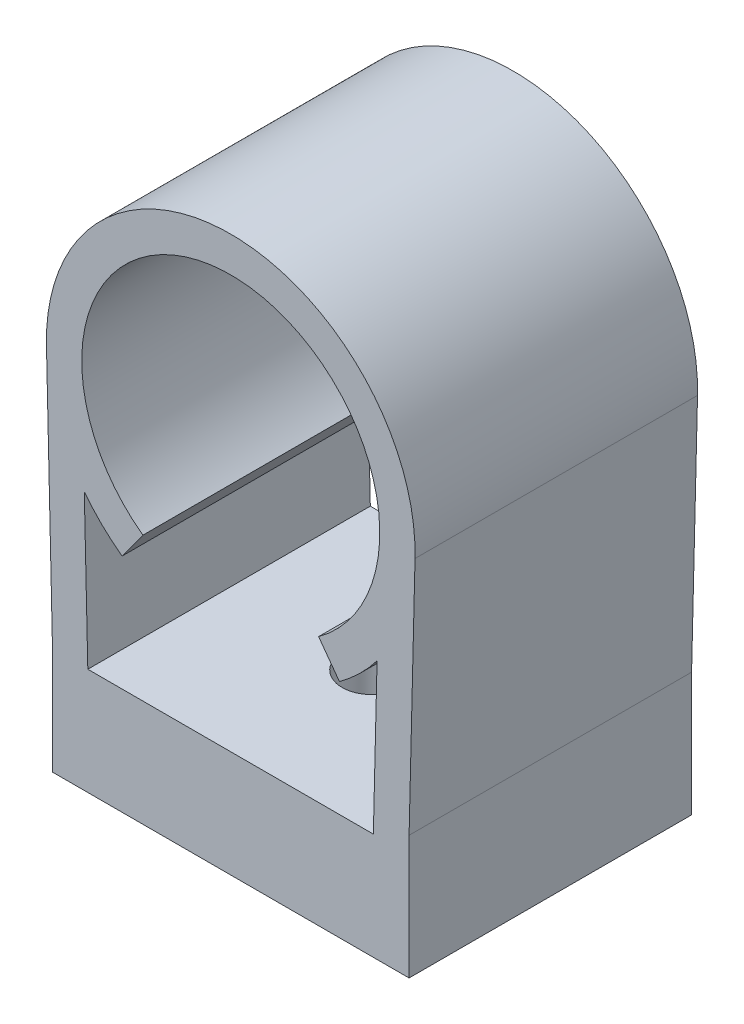
SolidWorks part; units mm, degrees
ref_plane "Front Plane" through (0, 0, 0) normal (0, 0, 1) x (1, 0, 0)
ref_plane "Top Plane" through (0, 0, 0) normal (0, 1, 0) x (1, 0, 0)
ref_plane "Right Plane" through (0, 0, 0) normal (1, 0, 0) x (0, 0, -1)
sketch "Sketch1" plane through (0, 0, 0) normal (0, 0, 1) x (1, 0, 0)
  line L0 (12.827, 0) -> (12.827, 26.67) construction
  line L1 (0, 0) -> (25.654, 0)
  line L2 (0, 0) -> (0, 7.874)
  line L3 (2.5452, 7.6792) -> (23.0836, 7.6792)
  line L4 (25.654, 0) -> (25.654, 8.89)
  line L5 (0, 7.874) -> (-0.4282, 26.363)
  line L6 (25.654, 8.89) -> (26.0818, 26.3451)
  line L7 (2.5452, 7.6792) -> (2.2918, 18.6198)
  line L8 (23.0836, 7.6792) -> (23.3514, 18.6057)
  line L10 (5.0096, 15.961) -> (6.5072, 18.0125)
  line L11 (20.6444, 15.961) -> (19.1468, 18.0125)
  arc A0 (19.1468, 18.0125) -> (6.5072, 18.0125) centre (12.827, 26.67) ccw
  arc A1 (26.0818, 26.3451) -> (-0.4282, 26.363) centre (12.827, 26.67) ccw
  arc A2 (2.2918, 18.6198) -> (5.0096, 15.961) centre (12.827, 26.67) ccw
  arc A3 (20.6444, 15.961) -> (23.3514, 18.6057) centre (12.827, 26.67) ccw
  point P17 (12.827, 15.9512)
  dimension "D2" = 21.4376
  dimension "D5" = 2.54
  dimension "D1" = 26.67
  dimension "D3" = 7.874
  dimension "D4" = 25.654
  dimension "D6" = 2.54
  dimension "D7" = 2.54
  dimension "D8" = 20.5384
  dimension "D9" = 1.404
extrude "Boss-Extrude1" add sketch "Sketch1" along normal blind 20.32
hole_wizard "#8 Clearance Hole1" positions "Sketch2" profile "Sketch4" hole size "#8" standard "ANSI Inch" end condition up to next
sketch "Sketch2" plane through (0, 0, 0) normal (0, -1, 0) x (-1, 0, 0)
  line L0 (-25.654, 0) -> (0, -20.32) construction
  point P8 (-12.827, -10.16)
sketch "Sketch4" plane through (12.827, 0, 10.16) normal (1, 0, 0) x (0, 0, -1)
  line L0 (0, 0) -> (0, 7.6792)
  line L1 (0, 7.6792) -> (2.1526, 7.6792)
  line L2 (2.1526, 7.6792) -> (2.1526, 0)
  line L5 (2.1526, 0) -> (0, 0)
  line L11 (0, -6.35) -> (0, 107.95) construction
  dimension "Thru Hole Dia." = 4.3053
  dimension "Thru Hole Depth" = 7.6792
